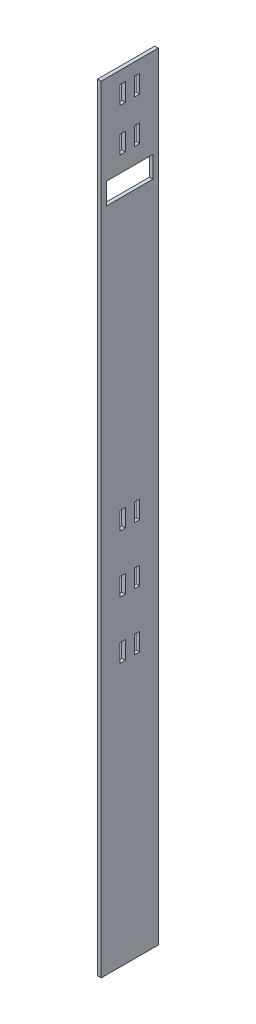
SolidWorks part; units mm, degrees
ref_plane "Front Plane" through (0, 0, 0) normal (0, 0, 1) x (1, 0, 0)
ref_plane "Top Plane" through (0, 0, 0) normal (0, 1, 0) x (1, 0, 0)
ref_plane "Right Plane" through (0, 0, 0) normal (1, 0, 0) x (0, 0, -1)
sketch "Sketch1" plane through (0, 0, 0) normal (1, 0, 0) x (0, 0, -1)
  line L1 (-25.4, 457.2) -> (25.4, 457.2)
  line L2 (-25.4, 457.2) -> (-25.4, -457.2)
  line L3 (-25.4, -457.2) -> (25.4, -457.2)
  line L4 (25.4, 457.2) -> (25.4, -457.2)
  line L5 (-25.4, 457.2) -> (25.4, -457.2) construction
  line L6 (-25.4, -457.2) -> (25.4, 457.2) construction
  point P0 (0, 0)
  dimension "D1" = 914.4
  dimension "D2" = 50.8
extrude "Boss-Extrude1" add sketch "Sketch1" along normal blind 3.175
sketch "Sketch2" plane through (3.175, 0, 0) normal (1, 0, 0) x (0, 0, -1)
  line L0 (-25.4, -457.2) -> (25.4, -457.2) construction
  line L1 (4, -201.6125) -> (8.7625, -201.6125)
  line L2 (4, -201.6125) -> (4, -217.4875)
  line L3 (4, -217.4875) -> (8.7625, -217.4875)
  line L4 (8.7625, -201.6125) -> (8.7625, -217.4875)
  line L5 (4, -201.6125) -> (8.7625, -217.4875) construction
  line L6 (4, -217.4875) -> (8.7625, -201.6125) construction
  point P0 (6.3813, -209.55)
  dimension "D1" = 4.7625
  dimension "D2" = 15.875
  dimension "D3" = 239.7125
  dimension "D4" = 4
extrude "Cut-Extrude1" cut sketch "Sketch2" against normal through all
mirror "Mirror1" about plane through (0, 0, 0) normal (0, 0, 1) of "Cut-Extrude1"
pattern_linear "LPattern1" count 2 spacing 50.8 along (0, 1, 0) count 2 spacing 50.8 along (0, -1, 0) of "Mirror1"
sketch "Sketch3" plane through (3.175, 0, 0) normal (1, 0, 0) x (0, 0, -1)
  line L0 (8.7625, -166.6875) -> (8.7625, -150.8125) construction
  line L1 (4, 138.1125) -> (8.7625, 138.1125)
  line L2 (4, 138.1125) -> (4, 122.2375)
  line L3 (4, 122.2375) -> (8.7625, 122.2375)
  line L4 (8.7625, 138.1125) -> (8.7625, 122.2375)
  line L5 (4, 138.1125) -> (8.7625, 122.2375) construction
  line L6 (4, 122.2375) -> (8.7625, 138.1125) construction
  line L7 (8.7625, -150.8125) -> (4, -150.8125) construction
  line L8 (4, -150.8125) -> (4, -166.6875) construction
  line L9 (0, 0) -> (0, 52.1648) construction
  line L10 (-4, 122.2375) -> (-8.7625, 138.1125) construction
  line L11 (-4, 138.1125) -> (-8.7625, 122.2375) construction
  line L12 (-8.7625, 138.1125) -> (-8.7625, 122.2375)
  line L13 (-4, 122.2375) -> (-8.7625, 122.2375)
  line L14 (-4, 138.1125) -> (-4, 122.2375)
  line L15 (-4, 138.1125) -> (-8.7625, 138.1125)
  point P0 (6.3812, 130.175)
  point P18 (-6.3812, 130.175)
  dimension "D1" = 273.05
extrude "Cut-Extrude2" cut sketch "Sketch3" against normal through all
pattern_linear "LPattern2" count 2 spacing 38.1 along (0, 1, 0) of "Cut-Extrude2"
sketch "Sketch4" plane through (3.175, 0, 0) normal (1, 0, 0) x (0, 0, -1)
  line L0 (0, -457.2) -> (0, 187.325) construction
  line L1 (-25.4, -457.2) -> (25.4, -457.2) construction
  line L2 (0, 187.325) -> (-25.4, 187.325)
  line L3 (-25.4, 457.2) -> (-25.4, -457.2) construction
  line L4 (-25.4, 187.325) -> (25.4, 187.325)
  line L5 (25.4, -457.2) -> (25.4, 457.2) construction
  line M30 (25.4, -457.2) -> (25.4, 457.2)
  line M31 (25.4, 457.2) -> (-25.4, 457.2)
  line M32 (-25.4, 457.2) -> (-25.4, -457.2)
  dimension "D1" = 644.525
extrude "Cut-Extrude3" cut sketch "Sketch4" against normal through all contours L2 L4 M30 M31 M32 region at (3.175, 322.2625, 0)
sketch "Sketch5" plane through (3.175, 0, 0) normal (1, 0, 0) x (0, 0, -1)
  line L0 (-25.4, -457.2) -> (-25.4, -501.65)
  line L1 (-25.4, -501.65) -> (25.4, -501.65)
  line L2 (25.4, -501.65) -> (25.4, -457.2)
  line L7 (25.4, -457.2) -> (25.4, 187.325)
  line L8 (25.4, 187.325) -> (-25.4, 187.325)
  line L9 (-25.4, 187.325) -> (-25.4, -457.2)
  line L10 (-25.4, -457.2) -> (25.4, -457.2)
  line L14 (-25.4, -457.2) -> (25.4, -457.2)
  dimension "D1" = 44.45
  dimension "D2" = 0
extrude "Boss-Extrude2" add sketch "Sketch5" against normal up to surface (3.175 mm away) up to face at (0, -158.75, 6.3813)
sketch "Sketch6" plane through (3.175, 0, 0) normal (1, 0, 0) x (0, 0, -1)
  line L1 (-20.6375, 108.0923) -> (20.6375, 108.0923)
  line L2 (-20.6375, 108.0923) -> (-20.6375, 89.0423)
  line L4 (20.6375, 108.0923) -> (20.6375, 89.0423)
  line L5 (0, 187.325) -> (0, 38.8722) construction
  line L6 (25.4, 187.325) -> (-25.4, 187.325) construction
  line L7 (-20.6375, 89.0423) -> (20.6375, 89.0423)
  line L8 (-22.225, 120.7923) -> (19.05, 120.7923) construction
  point P4 (19.05, 87.8933)
  point P5 (21.1337, 83.4844)
  point P6 (0, 108.0923)
  point P12 (19.05, 79.1954)
  dimension "D1" = 19.05
  dimension "D2" = 41.275
  dimension "D3" = 12.7
extrude "Cut-Extrude4" cut sketch "Sketch6" against normal through all contours L7 L4 L1 L2
